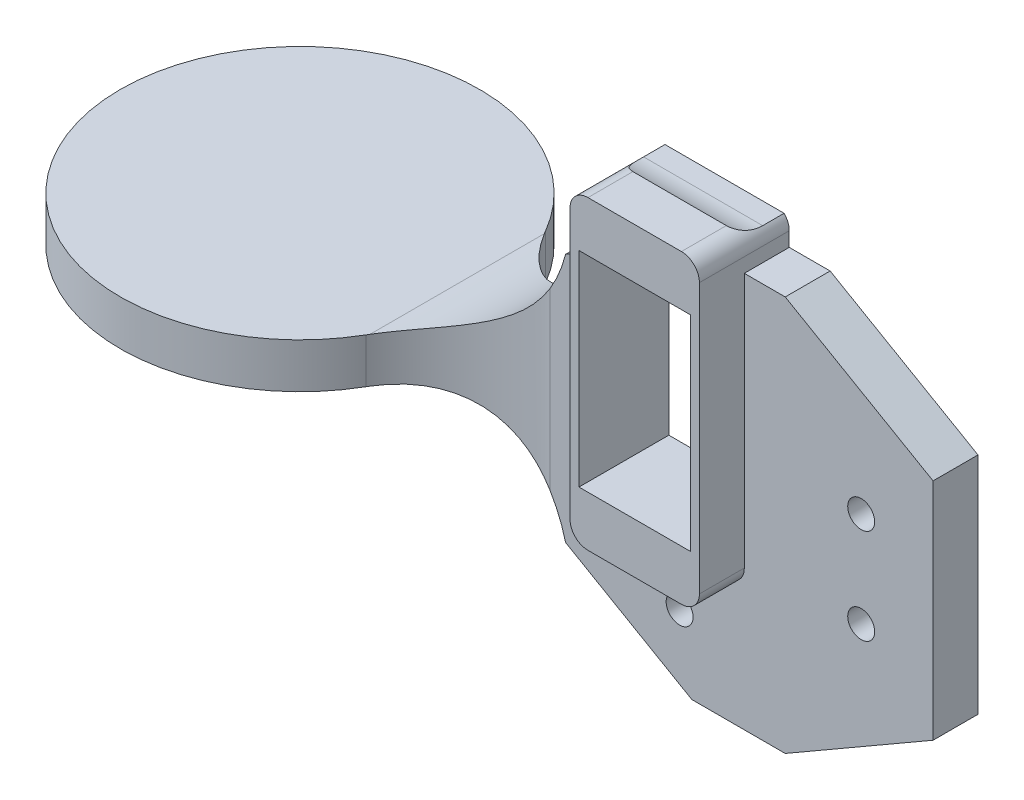
SolidWorks part; units mm, degrees
material "ABS"
ref_plane "Front Plane" through (0, 0, 0) normal (0, 0, 1) x (1, 0, 0)
ref_plane "Top Plane" through (0, 0, 0) normal (0, 1, 0) x (1, 0, 0)
ref_plane "Right Plane" through (0, 0, 0) normal (1, 0, 0) x (0, 0, -1)
other "Center of Mass"
sketch "Sketch1" plane through (0, 0, 0) normal (0, 1, 0) x (1, 0, 0)
  line L0 (0, 0) -> (128.1157, 0) construction
  line L2 (30.3109, -2.5) -> (82.5, -2.5)
  line L4 (30.3109, 2.5) -> (82.5, 2.5)
  line L5 (82.5, -2.5) -> (82.5, 2.5)
  arc A0 (17.3205, 10) -> (17.3205, -10) centre (0, 0) ccw
  arc A1 (30.3109, 2.5) -> (17.3205, 10) centre (30.3109, 17.5) cw
  arc A2 (17.3205, -10) -> (30.3109, -2.5) centre (30.3109, -17.5) cw
  point P3 (50, 0)
  dimension "D1" = 40
  dimension "D4" = 15
  dimension "D5" = 15
  dimension "D2" = 5
  dimension "D3" = 82.5
extrude "Boss-Extrude1" add sketch "Sketch1" along normal blind 5
sketch "Sketch4" plane through (82.5, 0, 0) normal (1, 0, 0) x (0, 0, -1)
  line L0 (0, 5) -> (0, 0) construction
  line L1 (-2.5, 5) -> (2.5, 5) construction
  line L3 (-2.5, -22.5) -> (2.5, -22.5)
  line L4 (-2.5, -22.5) -> (-2.5, 27.5)
  line L5 (-2.5, 27.5) -> (2.5, 27.5)
  line L6 (2.5, -22.5) -> (2.5, 27.5)
  line L7 (-2.5, -22.5) -> (2.5, 27.5) construction
  line L8 (-2.5, 27.5) -> (2.5, -22.5) construction
  point P5 (0, 2.5)
  dimension "D1" = 50
  dimension "D2" = 5
extrude "Boss-Extrude4" add sketch "Sketch4" against normal blind 50
fillet "Fillet1" radius 15 2 edges at (32.5, 0, 0) (32.5, 5, 0)
sketch "Sketch5" plane through (0, 0, 2.5) normal (0, 0, 1) x (1, 0, 0)
  line L0 (82.5, 2.5) -> (30.3109, 2.5) construction
  line L1 (82.5, 27.5) -> (82.5, -22.5) construction
  line L2 (30.3109, 12.1974) -> (30.3109, -7.1974) construction
  line L3 (57.5, 27.5) -> (57.5, -22.5) construction
  line L4 (32.5, 27.5) -> (82.5, 27.5) construction
  line L5 (32.5, -22.5) -> (82.5, -22.5) construction
  line L6 (56.4054, 2.5) -> (30.3109, 2.5) construction
  line L7 (32.5, 27.5) -> (32.5, 20) construction
  line L8 (32.5, 28.75) -> (57, 28.75)
  line L9 (32.5, 28.75) -> (32.5, -23.75)
  line L10 (32.5, -23.75) -> (57, -23.75)
  line L11 (57, 28.75) -> (57, -23.75)
  line L12 (32.5, 28.75) -> (57, -23.75) construction
  line L13 (32.5, -23.75) -> (57, 28.75) construction
  line L14 (44.75, -23.75) -> (44.75, 28.75) construction
  line L15 (38.55, -0.3) -> (50.95, 22.5) construction
  line L16 (38.55, 22.5) -> (50.95, 22.5)
  line L17 (38.55, 22.5) -> (38.55, -0.3)
  line L18 (38.55, -0.3) -> (50.95, -0.3)
  line L19 (50.95, 22.5) -> (50.95, -0.3)
  line L20 (38.55, 11.1) -> (50.95, 11.1) construction
  line L21 (51.95, -5.9) -> (37.55, -5.9)
  line L22 (51.95, -5.9) -> (51.95, 28.1)
  line L23 (51.95, 28.1) -> (37.55, 28.1)
  line L24 (37.55, -5.9) -> (37.55, 28.1)
  line L25 (51.95, -5.9) -> (37.55, 28.1) construction
  line L26 (51.95, 28.1) -> (37.55, -5.9) construction
  circle A0 centre (44.75, 16.5) radius 12.25
  circle A1 centre (44.75, -11.5) radius 12.25
  circle A2 centre (44.75, -11.5) radius 15.75
  circle A3 centre (64.9562, -2.7988) radius 1.5
  circle A4 centre (64.9562, -2.7988) radius 3
  circle A5 centre (64.9562, 7.7988) radius 3
  circle A6 centre (64.9562, 7.7988) radius 1.5
  circle A7 centre (44.75, -11.5) radius 1.5
  circle A8 centre (44.75, -11.5) radius 3
  point P13 (44.75, 2.5)
  point P30 (44.75, 11.1)
  dimension "D4" = 12.25
  dimension "D5" = 24.5
  dimension "D13" = 31.5
  dimension "D14" = 3
  dimension "D16" = 6
  dimension "D17" = 22
  dimension "D18" = 3
  dimension "D19" = 6
  dimension "D1" = 24.5
  dimension "D2" = 52.5
  dimension "D3" = 0
  dimension "D6" = 12.25
  dimension "D7" = 6
  dimension "D8" = 22.8
  dimension "D9" = 12.4
  dimension "D10" = 34
  dimension "D11" = 14.4
  dimension "D12" = 5.6
  dimension "D15" = 5.2988
sketch "Sketch6" plane through (0, 0, 2.5) normal (0, 0, 1) x (1, 0, 0)
  circle A0 centre (44.75, -11.5) radius 1.5
  dimension "D1" = 3
extrude "Cut-Extrude1" cut sketch "Sketch6" against normal through all
sketch "Sketch8" plane through (0, 0, 2.5) normal (0, 0, 1) x (1, 0, 0)
  line L0 (37.55, -5.9) -> (37.55, 28.1)
  line L1 (37.55, 28.1) -> (51.95, 28.1)
  line L2 (51.95, 28.1) -> (51.95, -5.9)
  line L3 (51.95, -5.9) -> (37.55, -5.9)
  dimension "D1" = 34
extrude "Boss-Extrude5" add sketch "Sketch8" along normal blind 5
sketch "Sketch9" plane through (0, 0, 7.5) normal (0, 0, 1) x (1, 0, 0)
  line L0 (38.55, 22.5) -> (50.95, 22.5)
  line L1 (50.95, 22.5) -> (50.95, -0.3)
  line L2 (50.95, -0.3) -> (38.55, -0.3)
  line L3 (38.55, -0.3) -> (38.55, 22.5)
extrude "Cut-Extrude2" cut sketch "Sketch9" against normal through all
fillet "Fillet2" radius 5 2 edges at (32.5, -22.5, 0) (32.5, 27.5, 0)
fillet "Fillet3" radius 2 4 edges at (51.95, -5.9, 5) (51.95, 28.1, 5) (37.55, 28.1, 5) (37.55, -5.9, 5)
fillet "Fillet4" radius 6 1 edges at (44.75, 27.5, 2.5)
sketch "Sketch10" plane through (0, 0, -2.5) normal (0, 0, -1) x (-1, 0, 0)
  circle A0 centre (-64.9562, -2.7988) radius 1.5
  circle A1 centre (-64.9562, 7.7988) radius 1.5
  dimension "D1" = 3
  dimension "D2" = 3
extrude "Cut-Extrude3" cut sketch "Sketch10" against normal through all
sketch "Sketch14" plane through (0, 0, 2.5) normal (0, 0, 1) x (1, 0, 0)
  line L0 (72.9562, 27.5) -> (72.9562, -22.5)
  line L1 (82.5, -22.5) -> (28.5, -22.5)
  line L2 (82.5, -22.5) -> (82.5, -19.5)
  line L3 (56.5017, -19.5) -> (28.5, -19.5)
  line L4 (28.5, -22.5) -> (28.5, -19.5)
  line L5 (51.3783, 27.5) -> (82.5, 27.5) construction
  line L6 (56.5017, 24.5) -> (28.5, 24.5)
  line L7 (82.5, 2.5) -> (17.3205, 2.5) construction
  line L8 (17.3205, 5) -> (17.3205, 0) construction
  line L9 (51.3055, 27.5) -> (29.6549, 15)
  line L10 (29.6549, 15) -> (29.6549, -10)
  line L11 (29.6549, -10) -> (51.3055, -22.5)
  line L12 (51.3055, -22.5) -> (72.9562, -10)
  line L13 (72.9562, -10) -> (72.9562, 15)
  line L14 (72.9562, 15) -> (51.3055, 27.5)
  circle A0 centre (51.3055, 2.5) radius 21.6506 construction
  circle A1 centre (64.9562, 7.7988) radius 3 construction
  line M5 (32.5, -15) -> (32.5, -17.5)
  arc M6 (32.5, -17.5) -> (37.5, -22.5) centre (37.5, -17.5) ccw
  line M7 (37.5, -22.5) -> (82.5, -22.5)
  line M8 (82.5, -22.5) -> (82.5, 27.5)
  line M9 (82.5, 27.5) -> (51.3783, 27.5)
  arc M10 (51.3783, 27.5) -> (51.95, 26.1) centre (49.95, 26.1) cw
  line M11 (51.95, 26.1) -> (51.95, -3.9)
  line M15 (37.55, -3.9) -> (37.55, 26.1)
  arc M16 (37.55, 26.1) -> (38.1217, 27.5) centre (39.55, 26.1) cw
  line M17 (38.1217, 27.5) -> (37.5, 27.5)
  arc M18 (37.5, 27.5) -> (32.5, 22.5) centre (37.5, 22.5) ccw
  line M19 (32.5, 22.5) -> (32.5, 20)
  arc M20 (32.5, 20) -> (30.3109, 12.1974) centre (17.5, 20) cw
  arc M24 (30.3109, -7.1974) -> (32.5, -15) centre (17.5, -15) cw
  dimension "D4" = 8
  dimension "D6" = 25
  dimension "D1" = 3
  dimension "D2" = 8
  dimension "D3" = 54
  dimension "D5" = 0
extrude "Cut-Extrude6" cut sketch "Sketch14" against normal blind 10 contours L11 L3 M24 M5 M6 | L11 L3 M6 M7 | L12 L1 L0 | L11 L12 L3 | L0 M9 M7 M8 | L14 L0 M9 M10 | L6 L14 M10 M11 | L9 L6 M15 M18 M19 M20 | L6 M15 M16 M17 M18 region at (77.7281, 2.5, 2.5) region at (65.7396, 23.3332, 2.5) region at (65.7393, -18.3333, 2.5) region at (53.4314, 25.4107, 2.5) region at (51.3055, -20.5, 2.5) region at (41.4922, -21.0298, 2.5) region at (37.0179, -16.8305, 2.5) region at (34.8161, 21.1656, 2.5) region at (35.7594, 25.7757, 2.5)
